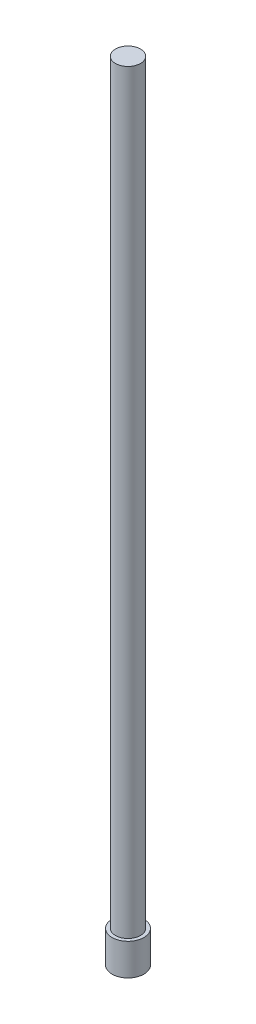
SolidWorks part; units mm, degrees
ref_plane "Front Plane" through (0, 0, 0) normal (0, 0, 1) x (1, 0, 0)
ref_plane "Top Plane" through (0, 0, 0) normal (0, 1, 0) x (1, 0, 0)
ref_plane "Right Plane" through (0, 0, 0) normal (1, 0, 0) x (0, 0, -1)
sketch "Sketch1" plane through (0, 0, 0) normal (0, 1, 0) x (1, 0, 0)
  circle A0 centre (0, 0) radius 1.025
  circle A1 centre (0, 0) radius 2
  dimension "D1" = 2.05
  dimension "D2" = 4
extrude "Boss-Extrude1" add sketch "Sketch1" along normal blind 3
sketch "Sketch2" plane through (0, 3, 0) normal (0, 1, 0) x (1, 0, 0)
  circle A0 centre (0, 0) radius 2
  circle A1 centre (0, 0) radius 2 construction
extrude "Boss-Extrude2" add sketch "Sketch2" along normal blind 1
sketch "Sketch3" plane through (0, 4, 0) normal (0, 1, 0) x (1, 0, 0)
  circle A0 centre (0, 0) radius 1.575
  dimension "D1" = 3.15
extrude "Boss-Extrude3" add sketch "Sketch3" along normal blind 95
